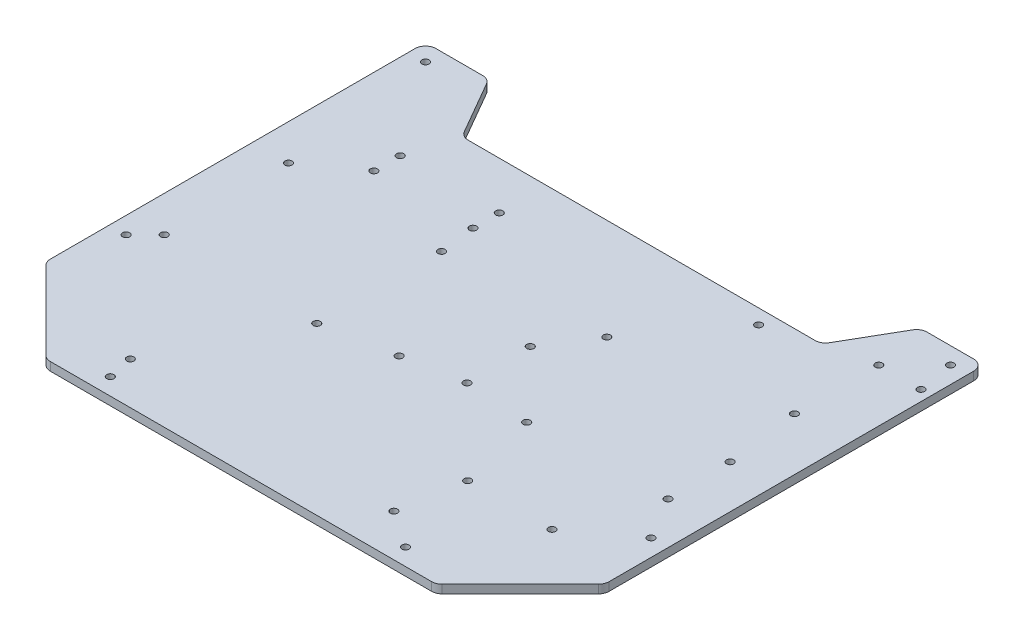
SolidWorks part; units mm, degrees
material "Acier non allié"
ref_plane "Front" through (0, 0, 0) normal (0, 0, 1) x (1, 0, 0)
ref_plane "Top" through (0, 0, 0) normal (0, 1, 0) x (1, 0, 0)
ref_plane "Right" through (0, 0, 0) normal (1, 0, 0) x (0, 0, -1)
sketch "Main scetch" plane through (0, 0, 0) normal (0, 1, 0) x (1, 0, 0)
  line L1 (0, 0) -> (132.5, 0) construction
  line L2 (0, 0) -> (0, 220) construction
  line L3 (0, 220) -> (132.5, 220) construction
  line L4 (132.5, 0) -> (132.5, 220) construction
  line L13 (-92.5, 0) -> (92.5, 0)
  line L14 (92.5, 0) -> (132.5, 40)
  line L15 (132.5, 40) -> (132.5, 220)
  line L16 (132.5, 220) -> (102.5, 220)
  line L17 (102.5, 220) -> (85.1795, 190)
  line L18 (85.1795, 190) -> (-85.1795, 190)
  line L19 (-102.5, 220) -> (-85.1795, 190)
  line L20 (-132.5, 220) -> (-102.5, 220)
  line L21 (-132.5, 40) -> (-132.5, 220)
  line L22 (-92.5, 0) -> (-132.5, 40)
  point P11 (0, 190)
  dimension "132.5" = 132.5
  dimension "D2" = 220
  dimension "D1" = 40
  dimension "D3" = 40
  dimension "D4" = 30
  dimension "D5" = 60
  dimension "D6" = 30
extrude "Main extrusion" add sketch "Main scetch" along normal blind 4
fillet "Congé1" radius 5 10 edges at (-132.5, 2, -40) (-92.5, 2, 0) (92.5, 2, 0) (132.5, 2, -40) (132.5, 2, -220) (102.5, 2, -220) (85.1795, 2, -190) (-85.1795, 2, -190) (-102.5, 2, -220) (-132.5, 2, -220)
sketch "Esquisse1" plane through (0, 4, 0) normal (0, 1, 0) x (1, 0, 0)
  line L0 (0, 0) -> (0, 218.5516) construction
  line L1 (132.5, 42.0711) -> (132.5, 215) construction
  line L2 (127.5, 220) -> (105.3868, 220) construction
  line L3 (-90.4289, 0) -> (90.4289, 0) construction
  circle A0 centre (70, 8) radius 1
  circle A1 centre (124.5, 70) radius 1
  circle A2 centre (124.5, 212) radius 1
  circle A3 centre (-124.5, 212) radius 1
  circle A4 centre (-124.5, 70) radius 1
  circle A5 centre (-70, 8) radius 1
  dimension "D1" = 2
  dimension "D2" = 2
  dimension "D3" = 2
  dimension "D4" = 8
  dimension "D5" = 8
  dimension "D6" = 8
  dimension "D7" = 8
  dimension "D8" = 70
  dimension "D9" = 70
extrude "Enlèv. mat.-Extru.1" cut sketch "Esquisse1" against normal through all
hole_wizard "Dégagement M31" positions "Esquisse2" profile "Esquisse3" hole size "M3" standard "ISO" end condition through all
sketch "Esquisse2" plane through (0, 4, 0) normal (0, 1, 0) x (1, 0, 0)
  point P0 (-124.5, 212)
  point P3 (-124.5, 70)
  point P6 (-70, 8)
  point P9 (70, 8)
  point P12 (124.5, 70)
  point P15 (124.5, 212)
sketch "Esquisse3" plane through (-124.5, 4, -212) normal (1, 0, 0) x (0, 0, 1)
  line L0 (0, 0) -> (0, 4)
  line L1 (0, 4) -> (1.7, 4)
  line L2 (1.7, 4) -> (1.7, 0)
  line L5 (1.7, 0) -> (0, 0)
  line L11 (0, -6.35) -> (0, 107.95) construction
  dimension "Diamètre du perçage jusqu'au prochain" = 3.4
  dimension "Profondeur du perçage jusqu'au prochain" = 4
sketch "Esquisse4" plane through (0, 4, 0) normal (0, 1, 0) x (1, 0, 0)
  line L0 (-132.5, 215) -> (-132.5, 42.0711) construction
  line L2 (82.2927, 190) -> (-82.2927, 190) construction
  line L3 (132.5, 42.0711) -> (132.5, 215) construction
  line L4 (-90.4289, 0) -> (90.4289, 0) construction
  line L5 (127.5, 220) -> (105.3868, 220) construction
  circle A1 centre (-68.5, 185) radius 1 construction
  circle A5 centre (62.5, 183) radius 1
  circle A6 centre (31.5, 142) radius 1
  circle A7 centre (107.5, 155) radius 1
  circle A8 centre (127.5, 195) radius 1
  circle A9 centre (112, 120) radius 1
  circle A10 centre (112.5, 90) radius 1
  circle A11 centre (17.2, 120) radius 1
  circle A12 centre (17.2, 90) radius 1
  circle A13 centre (47.5, 88) radius 1
  circle A14 centre (57.5, 50) radius 1
  circle A15 centre (97.5, 50) radius 1
  circle A16 centre (52.5, 20) radius 1
  circle A17 centre (-10, 85) radius 1
  circle A18 centre (-72.5, 20) radius 1
  circle A19 centre (107.5, 195) radius 1
  circle A23 centre (-115.5, 138) radius 1
  circle A24 centre (-42.86, 138) radius 1
  circle A25 centre (-115.5, 79.07) radius 1
  circle A26 centre (-42.8904, 78.82) radius 1
  circle A27 centre (-92, 167.5) radius 1
  circle A28 centre (-45, 167.5) radius 1
  circle A29 centre (-92, 155) radius 1
  circle A30 centre (-45, 155) radius 1
  dimension "D4" = 2
  dimension "D13" = 2
  dimension "D16" = 2
  dimension "D19" = 2
  dimension "D24" = 2
  dimension "D25" = 2
  dimension "D28" = 2
  dimension "D30" = 2
  dimension "D32" = 2
  dimension "D36" = 2
  dimension "D37" = 2
  dimension "D40" = 2
  dimension "D48" = 2
  dimension "D49" = 2
  dimension "D50" = 2
  dimension "D52" = 2
  dimension "D11" = 2
  dimension "D12" = 2
  dimension "D65" = 2
  dimension "D66" = 2
  dimension "D58" = 2
  dimension "D61" = 2
  dimension "D70" = 2
  dimension "D71" = 2
  dimension "D14" = 195
  dimension "D15" = 7
  dimension "D20" = 25
  dimension "D21" = 65
  dimension "D22" = 5
  dimension "D23" = 25
  dimension "D26" = 20.5
  dimension "D27" = 100
  dimension "D29" = 30
  dimension "D31" = 115.3
  dimension "D33" = 115.3
  dimension "D34" = 132
  dimension "D35" = 85
  dimension "D38" = 50
  dimension "D39" = 75
  dimension "D41" = 35
  dimension "D42" = 80
  dimension "D43" = 20
  dimension "D44" = 20
  dimension "D45" = 205
  dimension "D46" = 85
  dimension "D47" = 142.5
  dimension "D51" = 25
  dimension "D53" = 25
  dimension "D54" = 5
  dimension "D55" = 64
  dimension "D7" = 59.18
  dimension "D8" = 72.64
  dimension "D9" = 58.93
  dimension "D10" = 72.61
  dimension "D67" = 17
  dimension "D68" = 138
  dimension "D56" = 23.5
  dimension "D57" = 23.5
  dimension "D59" = 17.5
  dimension "D60" = 17.5
  dimension "D62" = 12.5
  dimension "D63" = 12.5
  dimension "D64" = 23.5
  dimension "D69" = 23.5
  dimension "D17" = 41
  dimension "D18" = 31
extrude "Enlèv. mat.-Extru.2" cut sketch "Esquisse4" against normal through all
hole_wizard "Dégagement M32" positions "Esquisse5" profile "Esquisse6" hole size "M3" standard "ISO" end condition through all
sketch "Esquisse5" plane through (0, 4, 0) normal (0, 1, 0) x (1, 0, 0)
  point P9 (17.2, 120)
  point P18 (31.5, 142)
  point P21 (62.5, 183)
  point P24 (107.5, 155)
  point P27 (127.5, 195)
  point P30 (112, 120)
  point P33 (112.5, 90)
  point P36 (47.5, 88)
  point P39 (17.2, 90)
  point P42 (57.5, 50)
  point P45 (97.5, 50)
  point P48 (-10, 85)
  point P51 (-72.5, 20)
  point P54 (52.5, 20)
  point P57 (107.5, 195)
  point P86 (-115.5, 138)
  point P89 (-42.86, 138)
  point P92 (-115.5, 79.07)
  point P95 (-42.8904, 78.82)
  point P102 (-92, 167.5)
  point P105 (-92, 155)
  point P108 (-45, 155)
  point P111 (-45, 167.5)
  point P126 (0, 0)
  point P127 (0, 0)
  point P128 (0, 0)
  point P129 (0, 0)
sketch "Esquisse6" plane through (17.2, 4, -120) normal (1, 0, 0) x (0, 0, 1)
  line L0 (0, 0) -> (0, 4)
  line L1 (0, 4) -> (1.7, 4)
  line L2 (1.7, 4) -> (1.7, 0)
  line L5 (1.7, 0) -> (0, 0)
  line L11 (0, -6.35) -> (0, 107.95) construction
  dimension "Diamètre du perçage jusqu'au prochain" = 3.4
  dimension "Profondeur du perçage jusqu'au prochain" = 4
equation "\"WIDTH\"= 300mm'Total width of the robot"
equation "\"LENGTH\"= 220mm'Total length of the robot"
equation "\"D2@Main scetch\" = \"LENGTH\""
equation "\"CUT_DEPTH\"= 45mm'Depth of the cut on the edges of the plate"
equation "\"Plate_th\"= 3mm'Thickness of the plate"
equation "\"D1\"= \"Plate_th\""
equation "\"D47@Esquisse4\"=(80+205)/2"
